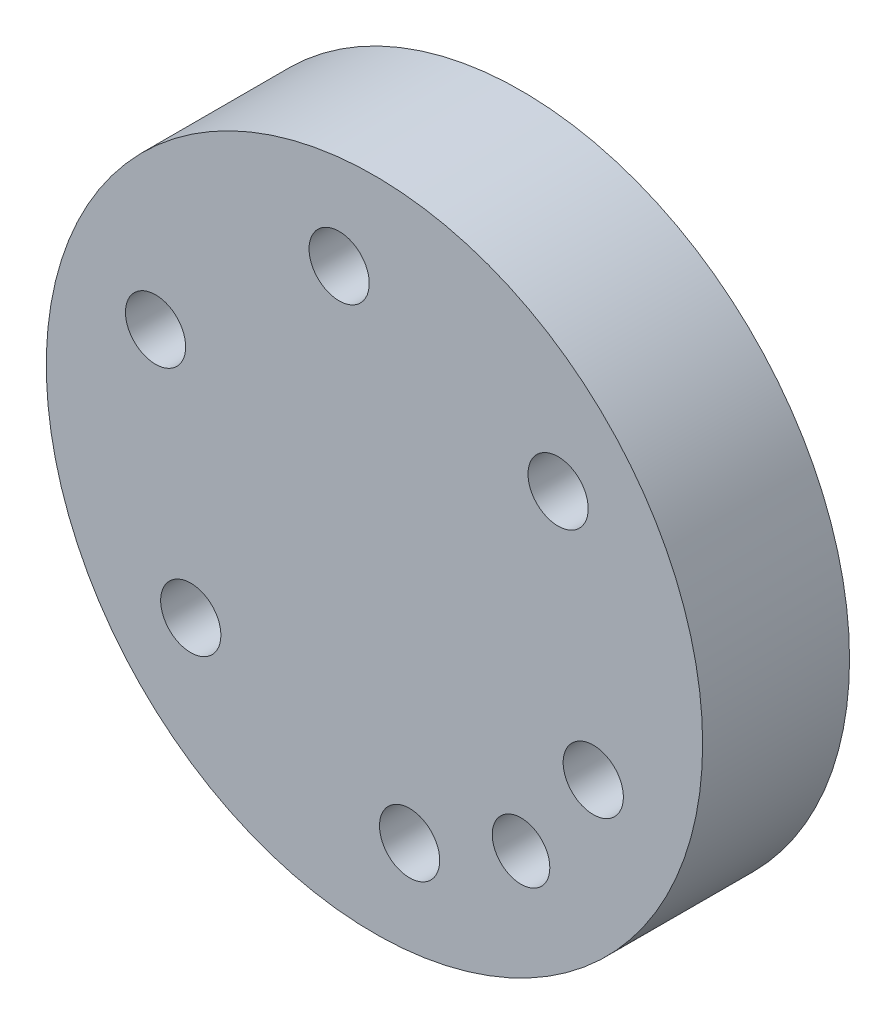
SolidWorks part; units mm, degrees
ref_plane "Front Plane" through (0, 0, 0) normal (0, 0, 1) x (1, 0, 0)
ref_plane "Top Plane" through (0, 0, 0) normal (0, 1, 0) x (1, 0, 0)
ref_plane "Right Plane" through (0, 0, 0) normal (1, 0, 0) x (0, 0, -1)
sketch "Sketch2" plane through (0, 0, 0) normal (0, 0, 1) x (1, 0, 0)
  circle A2 centre (22.3808, 278.1504) radius 88.7
  arc A4 (22.3808, 354.5504) -> (22.3808, 201.7504) centre (22.3808, 278.1504) ccw
  arc A5 (22.3808, 201.7504) -> (22.3808, 354.5504) centre (22.3808, 278.1504) ccw
  arc A6 (22.3808, 354.5504) -> (22.3808, 201.7504) centre (22.3808, 278.1504) ccw
  arc A7 (22.3808, 201.7504) -> (22.3808, 354.5504) centre (22.3808, 278.1504) ccw
  dimension "D2" = 177.4
  dimension "D1" = 0.2
extrude "Boss-Extrude1" add sketch "Sketch2" against normal offset from surface (24.7 mm away) 15.5
sketch "Sketch3" plane through (0, 0, 0) normal (0, 0, 1) x (1, 0, 0)
  circle A1 centre (22.3808, 278.1504) radius 88.7
  circle A2 centre (22.3808, 278.1504) radius 88.7
  circle A120 centre (12.8349, 340.868) radius 8.1375
  circle A121 centre (72.0102, 317.7343) radius 8.1375
  circle A122 centre (-36.7846, 301.2181) radius 8.1375
  circle A123 centre (-27.2648, 238.487) radius 8.1375
  circle A124 centre (31.8806, 215.335) radius 8.1375
  circle A125 centre (81.5193, 254.9712) radius 8.1375
  arc A126 (61.9965, 220.7534) -> (61.9965, 236.3127) centre (61.9965, 228.5331) ccw construction
  arc A127 (61.9965, 236.3127) -> (61.9965, 220.7534) centre (61.9965, 228.5331) ccw construction
  arc A128 (61.9965, 236.3127) -> (61.9965, 220.7534) centre (61.9965, 228.5331) ccw
  arc A129 (61.9965, 220.7534) -> (61.9965, 236.3127) centre (61.9965, 228.5331) ccw
  dimension "D2" = 16.275
  dimension "D1" = 0
extrude "Boss-Extrude2" add sketch "Sketch3" along normal blind 15
fillet "Fillet1" radius 2 1 edges at (69.7762, 228.5331, 0)
chamfer "Chamfer1" distance 4.5 distance2 8 1 edges at (22.3808, 201.7504, -24.7) first distance on face at (22.3808, 189.4504, -24.7)
fillet "Fillet2" radius 3 1 edges at (98.7808, 278.1504, -16.7)
fillet "Fillet3" radius 2 1 edges at (22.3808, 197.2504, -24.7)
